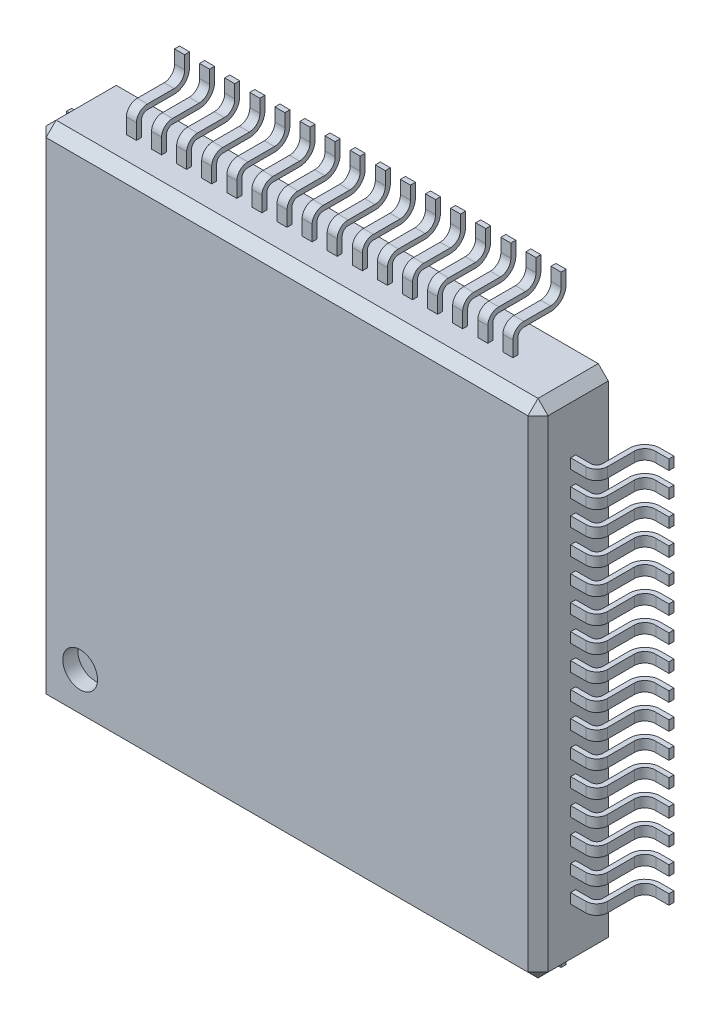
SolidWorks part; units mm, degrees
ref_plane "Plane1" through (0, 0, 0) normal (0, 0, 1) x (1, 0, 0)
ref_plane "Plane2" through (0, 0, 0) normal (0, 1, 0) x (1, 0, 0)
ref_plane "Plane3" through (0, 0, 0) normal (1, 0, 0) x (0, 0, -1)
sketch "Sketch1" plane through (0, 0, 0) normal (0, 0, 1) x (1, 0, 0)
  line L1 (0, 0) -> (10, 0)
  line L2 (0, 0) -> (0, 10)
  line L3 (0, 10) -> (10, 10)
  line L4 (10, 0) -> (10, 10)
  dimension "D1" = 10
  dimension "D2" = 10
extrude "Extrude1" add sketch "Sketch1" along normal blind 1.4
sketch "Sketch2" plane through (0, 0, 0) normal (0, -1, 0) x (1, 0, 0)
  line L1 (10, 0.7) -> (5, 0.7) construction
  line L2 (10, 1.4) -> (10, 0) construction
  line L5 (5, 1.4) -> (5, 0) construction
  line L7 (0, 1.4) -> (10, 1.4) construction
  line L8 (0, 0) -> (10, 0) construction
  line L9 (5.15, 0.65) -> (5.35, 0.65)
  line L10 (5.15, 0.65) -> (5.15, 0.75)
  line L11 (5.35, 0.65) -> (5.35, 0.75)
  line L12 (5.15, 0.75) -> (5.35, 0.75)
  line L13 (5.15, 0.65) -> (5.35, 0.75) construction
  line L14 (5.35, 0.65) -> (5.15, 0.75) construction
  line L15 (1.15, 0.65) -> (1.15, 0.75)
  line L16 (1.35, 0.65) -> (1.15, 0.65)
  line L17 (1.35, 0.65) -> (1.35, 0.75)
  line L18 (1.35, 0.75) -> (1.15, 0.75)
  line L19 (1.65, 0.65) -> (1.65, 0.75)
  line L20 (1.85, 0.65) -> (1.65, 0.65)
  line L21 (1.85, 0.65) -> (1.85, 0.75)
  line L22 (1.85, 0.75) -> (1.65, 0.75)
  line L23 (2.15, 0.65) -> (2.15, 0.75)
  line L24 (2.35, 0.65) -> (2.15, 0.65)
  line L25 (2.35, 0.65) -> (2.35, 0.75)
  line L26 (2.35, 0.75) -> (2.15, 0.75)
  line L27 (2.65, 0.65) -> (2.65, 0.75)
  line L28 (2.85, 0.65) -> (2.65, 0.65)
  line L29 (2.85, 0.65) -> (2.85, 0.75)
  line L30 (2.85, 0.75) -> (2.65, 0.75)
  line L31 (3.15, 0.65) -> (3.15, 0.75)
  line L32 (3.35, 0.65) -> (3.15, 0.65)
  line L33 (3.35, 0.65) -> (3.35, 0.75)
  line L34 (3.35, 0.75) -> (3.15, 0.75)
  line L35 (3.65, 0.65) -> (3.65, 0.75)
  line L36 (3.85, 0.65) -> (3.65, 0.65)
  line L37 (3.85, 0.65) -> (3.85, 0.75)
  line L38 (3.85, 0.75) -> (3.65, 0.75)
  line L39 (4.15, 0.65) -> (4.15, 0.75)
  line L40 (4.35, 0.65) -> (4.15, 0.65)
  line L41 (4.35, 0.65) -> (4.35, 0.75)
  line L42 (4.35, 0.75) -> (4.15, 0.75)
  line L43 (4.65, 0.65) -> (4.65, 0.75)
  line L44 (4.85, 0.65) -> (4.65, 0.65)
  line L45 (4.85, 0.75) -> (4.65, 0.75)
  line L46 (4.85, 0.65) -> (4.85, 0.75)
  line L75 (5.65, 0.75) -> (5.85, 0.75)
  line L76 (5.65, 0.65) -> (5.65, 0.75)
  line L77 (5.65, 0.65) -> (5.85, 0.65)
  line L78 (5.85, 0.65) -> (5.85, 0.75)
  line L79 (6.15, 0.75) -> (6.35, 0.75)
  line L80 (6.15, 0.65) -> (6.15, 0.75)
  line L81 (6.15, 0.65) -> (6.35, 0.65)
  line L82 (6.35, 0.65) -> (6.35, 0.75)
  line L83 (6.65, 0.75) -> (6.85, 0.75)
  line L84 (6.65, 0.65) -> (6.65, 0.75)
  line L85 (6.65, 0.65) -> (6.85, 0.65)
  line L86 (6.85, 0.65) -> (6.85, 0.75)
  line L87 (7.15, 0.75) -> (7.35, 0.75)
  line L88 (7.15, 0.65) -> (7.15, 0.75)
  line L89 (7.15, 0.65) -> (7.35, 0.65)
  line L90 (7.35, 0.65) -> (7.35, 0.75)
  line L91 (7.65, 0.75) -> (7.85, 0.75)
  line L92 (7.65, 0.65) -> (7.65, 0.75)
  line L93 (7.65, 0.65) -> (7.85, 0.65)
  line L94 (7.85, 0.65) -> (7.85, 0.75)
  line L95 (8.15, 0.75) -> (8.35, 0.75)
  line L96 (8.15, 0.65) -> (8.15, 0.75)
  line L97 (8.15, 0.65) -> (8.35, 0.65)
  line L98 (8.35, 0.65) -> (8.35, 0.75)
  line L99 (8.65, 0.75) -> (8.85, 0.75)
  line L100 (8.65, 0.65) -> (8.65, 0.75)
  line L101 (8.65, 0.65) -> (8.85, 0.65)
  line L102 (8.85, 0.65) -> (8.85, 0.75)
  point P12 (5.25, 0.7)
  dimension "D1" = 0.25
  dimension "D2" = 0.2
  dimension "D3" = 0.1
  dimension "D4" = 8
sketch "Sketch3" plane through (10, 0, 0) normal (1, 0, 0) x (0, 0, -1)
  line L0 (-1.4935, -1) -> (0.1604, -1) construction
  line L3 (-0.7, 0) -> (-0.7, -1.5011) construction
  line L4 (-1.4935, -0.4696) -> (0.1604, -0.4696) construction
  line L5 (0.2582, 0) -> (0.2582, -1.199) construction
  line L6 (-0.7, 0) -> (-0.7, -0.3042)
  line L7 (-0.5308, -0.4696) -> (0, -0.4696)
  line L8 (0.2582, -0.7421) -> (0.2582, -1)
  line L12 (-1.4, 0) -> (0, 0) construction
  arc A0 (-0.5308, -0.4696) -> (-0.7, -0.3042) centre (-0.5308, -0.3003) cw
  arc A1 (0, -0.4696) -> (0.2582, -0.7421) centre (0, -0.7282) cw
  dimension "D1" = 1
sweep "Sweep1" add profiles "Sketch2" path "Sketch3"
ref_plane "Plane4" through (0, 0, 0) normal (-0.7071, 0.7071, 0) x (-0.7071, -0.7071, 0)
mirror "Mirror1" about plane through (0, 0, 0) normal (-0.7071, 0.7071, 0) of "Sweep1"
ref_plane "Plane5" through (5, 5, 0) normal (-0.7071, -0.7071, 0) x (0.7071, -0.7071, 0)
mirror "Mirror2" about plane through (5, 5, 0) normal (-0.7071, -0.7071, 0) of "Mirror1", "Sweep1"
chamfer "Chamfer1" distance 0.2 angle 45 8 edges at (0, 0, 0.7) (5, 0, 1.4) (0, 5, 1.4) (0, 10, 0.7) (10, 0, 0.7) (10, 10, 0.7) (5, 10, 1.4) (10, 5, 1.4)
sketch "Эскиз1" plane through (0, 0, 1.4) normal (0, 0, 1) x (1, 0, 0)
  circle A0 centre (0.8789, 0.9587) radius 0.346
extrude "Вырез-Вытянуть1" cut sketch "Эскиз1" against normal blind 0.3
